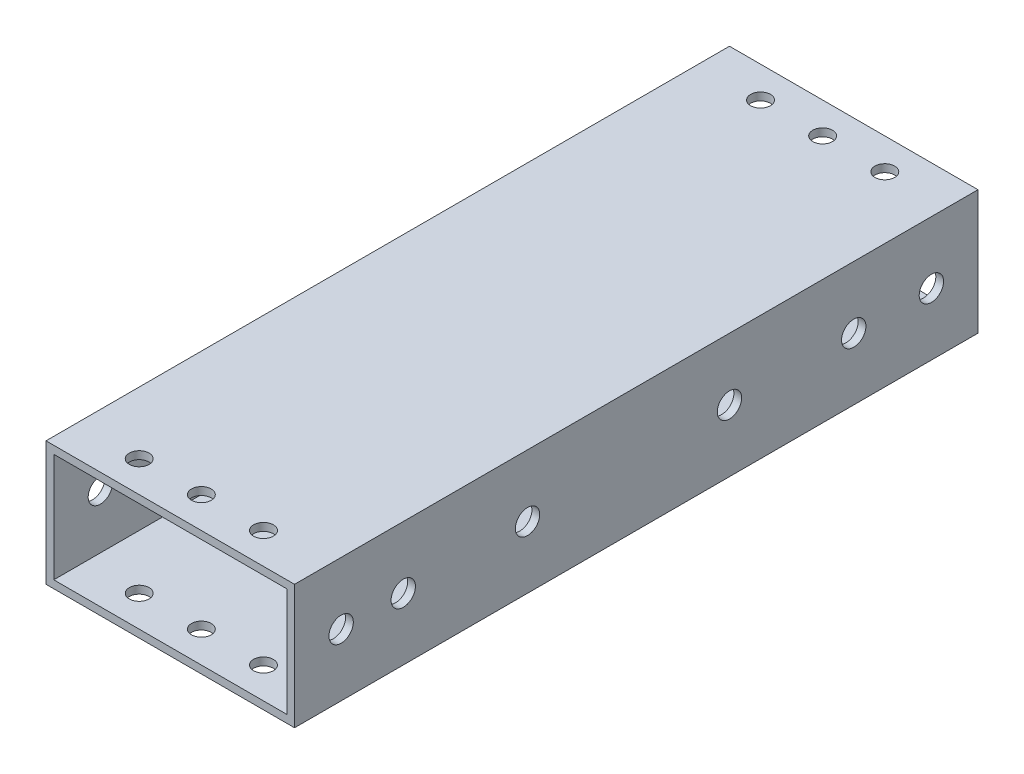
SolidWorks part; units mm, degrees
material "6061-T6 (SS)"
ref_plane "Front Plane" through (0, 0, 0) normal (0, 0, 1) x (1, 0, 0)
ref_plane "Top Plane" through (0, 0, 0) normal (0, 1, 0) x (1, 0, 0)
ref_plane "Right Plane" through (0, 0, 0) normal (1, 0, 0) x (0, 0, -1)
sketch "Sketch1" plane through (0, 0, 0) normal (0, 0, 1) x (1, 0, 0)
  line L0 (-23.8125, 11.1125) -> (23.8125, 11.1125)
  line L1 (-25.4, -12.7) -> (25.4, -12.7)
  line L2 (-25.4, -12.7) -> (-25.4, 12.7)
  line L3 (-25.4, 12.7) -> (25.4, 12.7)
  line L4 (25.4, -12.7) -> (25.4, 12.7)
  line L5 (-25.4, -12.7) -> (25.4, 12.7) construction
  line L6 (-25.4, 12.7) -> (25.4, -12.7) construction
  line L7 (23.8125, -11.1125) -> (23.8125, 11.1125)
  line L8 (-23.8125, -11.1125) -> (23.8125, -11.1125)
  line L9 (-23.8125, -11.1125) -> (-23.8125, 11.1125)
  point P0 (0, 0)
  dimension "D1" = 50.8
  dimension "D2" = 25.4
  dimension "D3" = 1.5875
extrude "Boss-Extrude1" add sketch "Sketch1" along normal mid plane 139.7
sketch "Sketch2" plane through (0, 12.7, 0) normal (0, 1, 0) x (1, 0, 0)
  line L0 (25.4, 69.85) -> (-25.4, 69.85) construction
  line L1 (25.4, 0) -> (-25.4, 0) construction
  line L2 (25.4, -69.85) -> (25.4, 69.85) construction
  line L3 (-25.4, -69.85) -> (-25.4, 69.85) construction
  circle A0 centre (-12.7, 63.5) radius 2.0193
  circle A1 centre (0, 63.5) radius 2.0193
  circle A2 centre (12.7, 63.5) radius 2.0193
  circle A3 centre (12.7, -63.5) radius 2.0193
  circle A4 centre (0, -63.5) radius 2.0193
  circle A5 centre (-12.7, -63.5) radius 2.0193
  dimension "D1" = 4.0386
  dimension "D2" = 12.7
  dimension "D3" = 12.7
  dimension "D4" = 6.35
extrude "Cut-Extrude1" cut sketch "Sketch2" against normal through all
sketch "Sketch3" plane through (25.4, 0, 0) normal (1, 0, 0) x (0, 0, -1)
  line L0 (0, 12.7) -> (0, -12.7) construction
  line L1 (-69.85, 12.7) -> (69.85, 12.7) construction
  line L2 (-69.85, -12.7) -> (69.85, -12.7) construction
  line L5 (69.85, -12.7) -> (69.85, 12.7) construction
  circle A8 centre (60.325, 0) radius 2.4892
  circle A9 centre (44.45, 0) radius 2.4892
  circle A10 centre (19.05, 0) radius 2.4892
  circle A11 centre (-60.325, 0) radius 2.4892
  circle A14 centre (-47.625, 0) radius 2.4892
  circle A15 centre (-22.225, 0) radius 2.4892
  point P15 (0, 0)
  dimension "D1" = 9.525
  dimension "D3" = 25.4
  dimension "D8" = 4.9784
  dimension "D2" = 12.7
  dimension "D6" = 15.875
  dimension "D7" = 25.4
extrude "Cut-Extrude2" cut sketch "Sketch3" against normal through all
